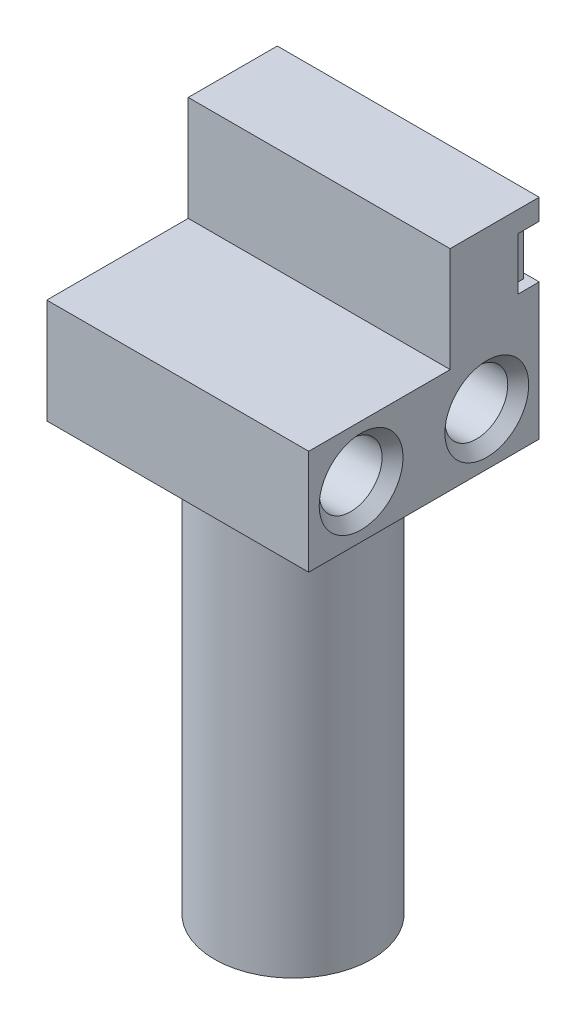
SolidWorks part; units mm, degrees
ref_plane "Front Plane" through (0, 0, 0) normal (0, 0, 1) x (1, 0, 0)
ref_plane "Top Plane" through (0, 0, 0) normal (0, 1, 0) x (1, 0, 0)
ref_plane "Right Plane" through (0, 0, 0) normal (1, 0, 0) x (0, 0, -1)
sketch "Sketch1" plane through (0, 0, 0) normal (0, 1, 0) x (1, 0, 0)
  line L1 (-12.5, 11) -> (12.5, 11)
  line L2 (-12.5, 11) -> (-12.5, -11)
  line L3 (-12.5, -11) -> (12.5, -11)
  line L4 (12.5, 11) -> (12.5, -11)
  line L5 (-12.5, 11) -> (12.5, -11) construction
  line L6 (-12.5, -11) -> (12.5, 11) construction
  point P0 (0, 0)
  dimension "D1" = 22
  dimension "D2" = 25
extrude "Boss-Extrude1" add sketch "Sketch1" along normal blind 10
sketch "Sketch2" plane through (12.5, 0, 0) normal (1, 0, 0) x (0, 0, -1)
  line L0 (-11, 10) -> (-11, 0) construction
  line L1 (-11, 0) -> (11, 0) construction
  line L2 (11, 10) -> (11, 0) construction
  circle A0 centre (-6, 5) radius 3
  circle A1 centre (6, 5) radius 3
  dimension "D1" = 5
  dimension "D3" = 5
  dimension "D2" = 5
extrude "Cut-Extrude1" cut sketch "Sketch2" against normal through all
chamfer "Chamfer1" distance 1 angle 45 4 edges at (-12.5, 5, -9) (-12.5, 5, 3) (12.5, 5, -9) (12.5, 5, 3)
sketch "Sketch3" plane through (0, 10, 0) normal (0, 1, 0) x (1, 0, 0)
  line L0 (-12.5, 11) -> (-12.5, 2.5)
  line L1 (-12.5, 11) -> (-12.5, -11) construction
  line L2 (-12.5, 2.5) -> (12.5, 2.5)
  line L3 (12.5, -11) -> (12.5, 11) construction
  line L4 (12.5, 2.5) -> (12.5, 11)
  line L5 (12.5, 11) -> (-12.5, 11)
  dimension "D1" = 8.5
extrude "Boss-Extrude2" add sketch "Sketch3" along normal blind 10
ref_plane "Plane1" through (0, 18, 0) normal (0, 1, 0) x (1, 0, 0)
sketch "Sketch4" plane through (0, 18, 0) normal (0, 1, 0) x (1, 0, 0)
  line L0 (-12.5, 11) -> (-12.5, 2.5) construction
  line L1 (12.5, 2.5) -> (12.5, 11) construction
  line L2 (12.5, 11) -> (-12.5, 11) construction
  line L3 (-12.5, 11) -> (-12.5, 9)
  line L4 (12.5, 9) -> (12.5, 11)
  line L5 (12.5, 11) -> (-12.5, 11)
  line L6 (12.5, 9) -> (-12.5, 9)
  line L7 (11.5, 9) -> (11.5, 10.5)
  line L8 (-12.5, 10.5) -> (12.5, 10.5)
  line L9 (10.5, 9) -> (10.5, 10.5)
  line L10 (9.5, 9) -> (9.5, 10.5)
  line L11 (7.5, 9) -> (7.5, 10.5)
  line L12 (8.5, 9) -> (8.5, 10.5)
  line L13 (6.5, 9) -> (6.5, 10.5)
  line L14 (5.5, 9) -> (5.5, 10.5)
  line L15 (3.5, 9) -> (3.5, 10.5)
  line L16 (4.5, 9) -> (4.5, 10.5)
  line L17 (-4.5, 9) -> (-4.5, 10.5)
  line L18 (-3.5, 9) -> (-3.5, 10.5)
  line L19 (-2.5, 9) -> (-2.5, 10.5)
  line L20 (-1.5, 9) -> (-1.5, 10.5)
  line L21 (0.5, 9) -> (0.5, 10.5)
  line L22 (-0.5, 9) -> (-0.5, 10.5)
  line L23 (1.5, 9) -> (1.5, 10.5)
  line L24 (2.5, 9) -> (2.5, 10.5)
  line L25 (-9.5, 9) -> (-9.5, 10.5)
  line L26 (-8.5, 9) -> (-8.5, 10.5)
  line L27 (-7.5, 9) -> (-7.5, 10.5)
  line L28 (-6.5, 9) -> (-6.5, 10.5)
  line L29 (-5.5, 9) -> (-5.5, 10.5)
  line L30 (-11.5, 9) -> (-11.5, 10.5)
  line L31 (-10.5, 9) -> (-10.5, 10.5)
  dimension "D1" = 2
  dimension "D2" = 1
  dimension "D3" = 0.5
extrude "Cut-Extrude2" cut sketch "Sketch4" against normal blind 5 contours L3 L8 L4 L5 | L8 L7 L6 L4 | L10 L6 L9 L8 | L6 L12 L8 L11 | L14 L6 L13 L8 | L6 L16 L8 L15 | L6 L24 L8 L23 | L22 L6 L21 L8 | L6 L20 L8 L19 | L6 L18 L8 L17 | L6 L29 L8 L28 | L6 L27 L8 L26 | L31 L6 L25 L8 | L6 L30 L8 L3 region at (0, 18, -10.75) region at (-12, 18, -9.75) region at (12, 18, -9.75) region at (-10, 18, -9.75) region at (10, 18, -9.75) region at (-8, 18, -9.75) region at (8, 18, -9.75) region at (-6, 18, -9.75) region at (6, 18, -9.75) region at (-4, 18, -9.75) region at (4, 18, -9.75) region at (-2, 18, -9.75) region at (2, 18, -9.75) region at (0, 18, -9.75)
sketch "Sketch5" plane through (0, 0, 0) normal (0, -1, 0) x (-1, 0, 0)
  circle A0 centre (0, 0) radius 7.5
  dimension "D1" = 15
extrude "Boss-Extrude3" add sketch "Sketch5" along normal blind 40
